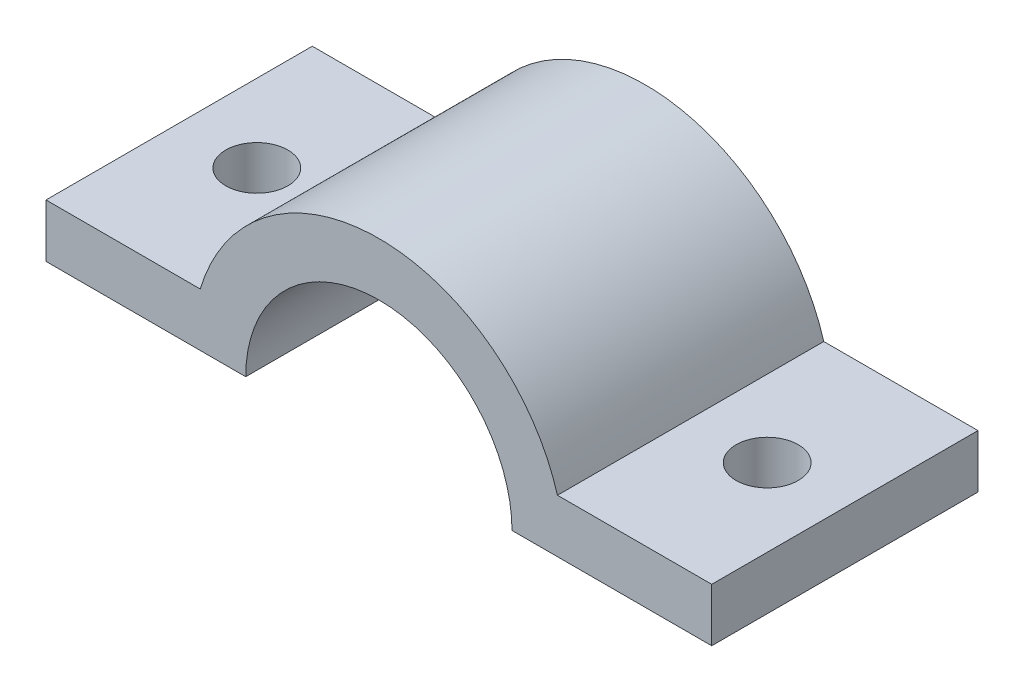
SolidWorks part; units mm, degrees
ref_plane "Plano frontal" through (0, 0, 0) normal (0, 0, 1) x (1, 0, 0)
ref_plane "Plano superior" through (0, 0, 0) normal (0, 1, 0) x (1, 0, 0)
ref_plane "Plano direito" through (0, 0, 0) normal (1, 0, 0) x (0, 0, -1)
sketch "Esboço1" plane through (0, 0, 0) normal (0, 0, 1) x (1, 0, 0)
  line L0 (15, 0) -> (37.5, 0)
  line L1 (37.5, 0) -> (37.5, 6)
  line L2 (37.5, 6) -> (20.1246, 6)
  line L3 (-15, 0) -> (-37.5, 0)
  line L4 (-37.5, 0) -> (-37.5, 6)
  line L5 (-37.5, 6) -> (-20.1246, 6)
  line L6 (0, 0) -> (0, 93.0486) construction
  arc A1 (15, 0) -> (-15, 0) centre (0, 0) ccw
  arc A2 (20.1246, 6) -> (-20.1246, 6) centre (0, 0) ccw
  dimension "D2" = 21
  dimension "D3" = 15
  dimension "D1" = 6
  dimension "D4" = 75
extrude "Ressalto-extrusão1" add sketch "Esboço1" along normal mid plane 30
hole_wizard "Furo de diâmetro Ø7.0 (7)1" positions "Esboço3" profile "Esboço2" hole size "Ø7.0" standard "ISO" end condition through all
sketch "Esboço3" plane through (0, 6, 0) normal (0, 1, 0) x (1, 0, 0)
  line L0 (0, 0) -> (0, 23.7705) construction
  line L3 (-55.8301, 0) -> (47.7847, 0) construction
  point P14 (-28.75, 0)
  point P16 (28.75, 0)
  dimension "D1" = 57.5
sketch "Esboço2" plane through (-28.75, 6, 0) normal (1, 0, 0) x (0, 0, 1)
  line L0 (0, 0) -> (0, 6)
  line L1 (0, 6) -> (3.5, 6)
  line L2 (3.5, 6) -> (3.5, 0)
  line L5 (3.5, 0) -> (0, 0)
  line L11 (0, -6.35) -> (0, 107.95) construction
  dimension "Thru Hole Dia." = 7
  dimension "Thru Hole Depth" = 6
